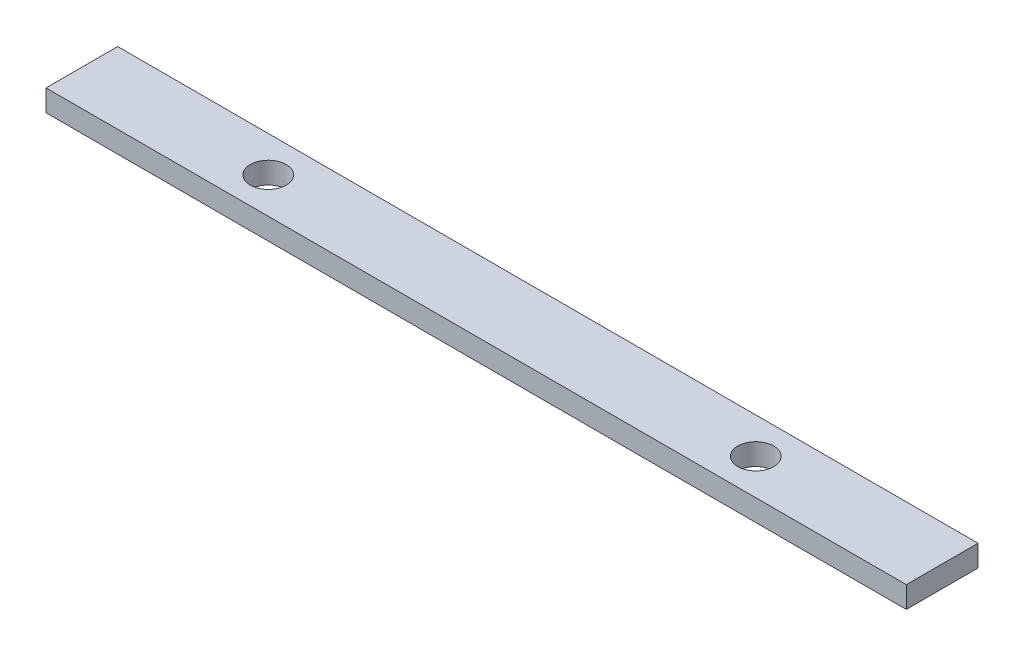
SolidWorks part; units mm, degrees
ref_plane "Front Plane" through (0, 0, 0) normal (0, 0, 1) x (1, 0, 0)
ref_plane "Top Plane" through (0, 0, 0) normal (0, 1, 0) x (1, 0, 0)
ref_plane "Right Plane" through (0, 0, 0) normal (1, 0, 0) x (0, 0, -1)
sketch "Sketch3" plane through (0, 0, 0) normal (0, 1, 0) x (1, 0, 0)
  line L1 (-60, -5) -> (60, -5)
  line L2 (-60, -5) -> (-60, 5)
  line L3 (-60, 5) -> (60, 5)
  line L4 (60, -5) -> (60, 5)
  line L5 (-60, -5) -> (60, 5) construction
  line L6 (-60, 5) -> (60, -5) construction
  point P0 (0, 0)
  dimension "D1" = 120
  dimension "D2" = 10
extrude "Boss-Extrude1" add sketch "Sketch3" along normal blind 3
sketch "Sketch5" plane through (0, 0, 0) normal (0, 1, 0) x (1, 0, 0)
  line L0 (-64.2904, 0) -> (64.0944, 0) construction
  line L1 (0, 30.7056) -> (0, -26.5382) construction
  circle A0 centre (-34, 0) radius 2.5
  circle A1 centre (34, 0) radius 2.5
  dimension "D1" = 5
  dimension "D2" = 34
extrude "Cut-Extrude1" cut sketch "Sketch5" along normal up to surface (3 mm away) up to face at (0, 3, 0)
